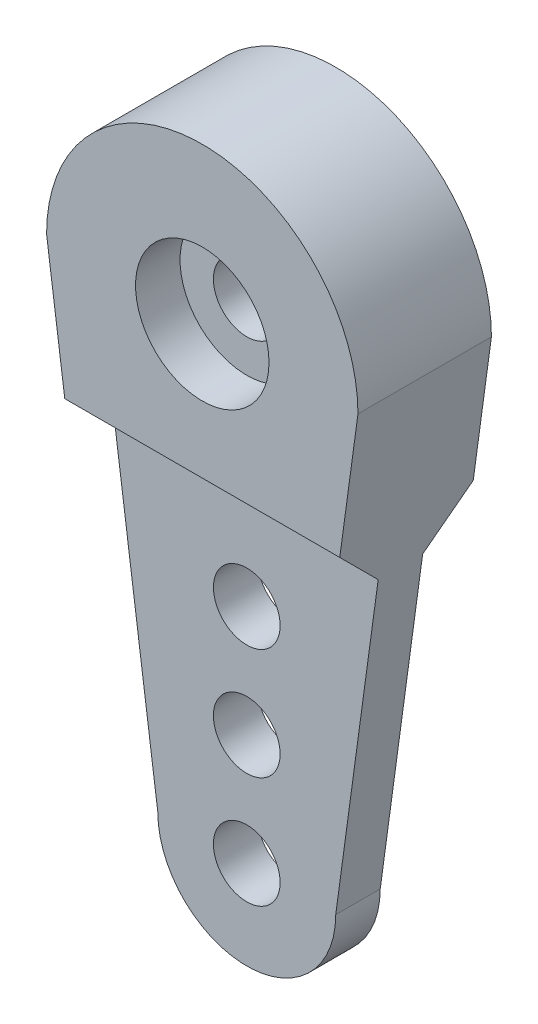
SolidWorks part; units mm, degrees
ref_plane "Front Plane" through (0, 0, 0) normal (0, 0, 1) x (1, 0, 0)
ref_plane "Top Plane" through (0, 0, 0) normal (0, 1, 0) x (1, 0, 0)
ref_plane "Right Plane" through (0, 0, 0) normal (1, 0, 0) x (0, 0, -1)
sketch "Sketch1" plane through (0, 0, 0) normal (0, 0, 1) x (1, 0, 0)
  line L0 (-7, 0) -> (-4, -22)
  line L1 (7, 0) -> (4, -22)
  arc A0 (7, 0) -> (-7, 0) centre (0, 0) ccw
  arc A1 (-4, -22) -> (4, -22) centre (0, -22) ccw
  dimension "D1" = 14
  dimension "D2" = 8
  dimension "D3" = 22
extrude "Boss-Extrude1" add sketch "Sketch1" along normal mid plane 2
sketch "Sketch2" plane through (0, 0, 0) normal (0, 0, 1) x (1, 0, 0)
  line L0 (4, -22) -> (7, 0) construction
  line L1 (-7, 0) -> (-4, -22) construction
  line L2 (5.9091, -8) -> (7, 0)
  line L3 (-7, 0) -> (-5.9091, -8)
  line L4 (0, 7) -> (8.9249, 7) construction
  line L5 (-5.9091, -8) -> (5.9091, -8)
  arc A0 (7, 0) -> (-7, 0) centre (0, 0) ccw construction
  arc A1 (7, 0) -> (-7, 0) centre (0, 0) ccw
  circle A2 centre (0, 0) radius 3
  dimension "D2" = 6
  dimension "D1" = 15
extrude "Boss-Extrude2" add sketch "Sketch2" along normal mid plane 6
chamfer "Chamfer1" distance 2 angle 45 2 edges at (0, -8, -3) (0, -8, 3)
sketch "Sketch3" plane through (0, 0, 1) normal (0, 0, 1) x (1, 0, 0)
  line L0 (0, -22) -> (0, -17.1372) construction
  line L1 (0, -22) -> (0, -17) construction
  circle A0 centre (0, -22) radius 1.5
  circle A1 centre (0, -17) radius 1.5
  circle A2 centre (0, -12) radius 1.5
  dimension "D1" = 3
  dimension "D3" = 5
  dimension "D2" = 3
extrude "Cut-Extrude1" cut sketch "Sketch3" against normal through all
sketch "Sketch4" plane through (0, 0, 1) normal (0, 0, 1) x (1, 0, 0)
  circle A0 centre (0, 0) radius 1.5
  dimension "D1" = 3
extrude "Cut-Extrude2" cut sketch "Sketch4" against normal through all
